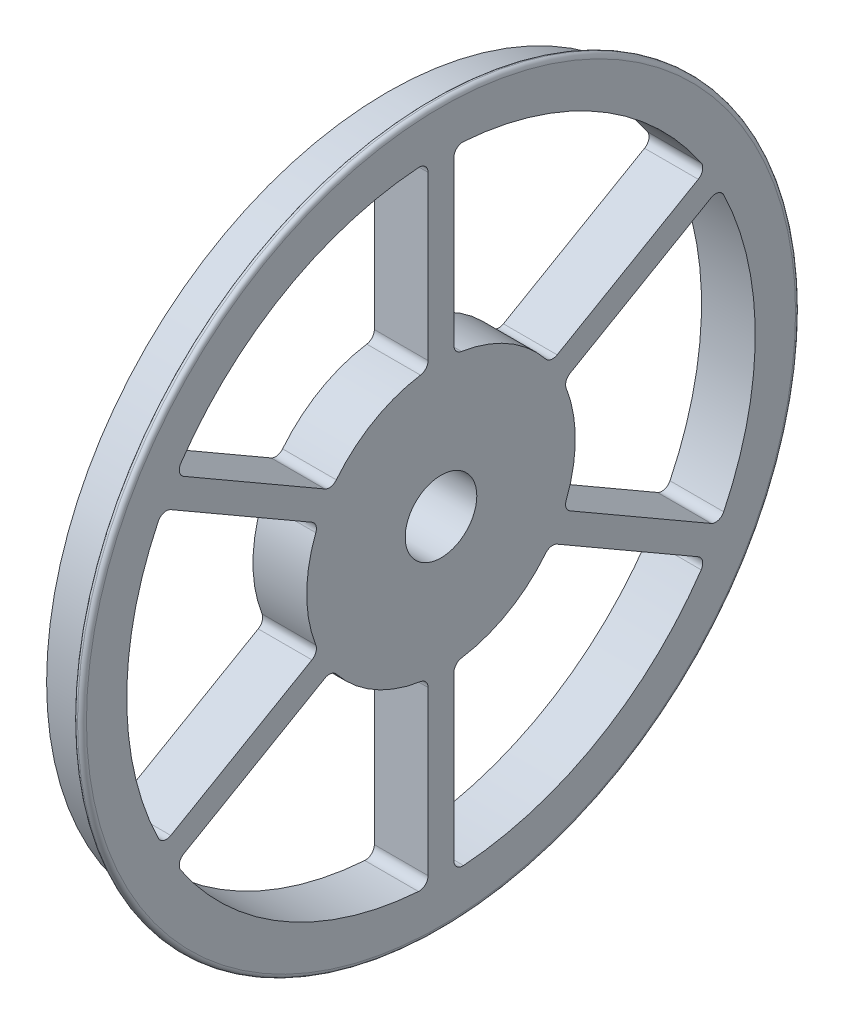
SolidWorks part; units mm, degrees
ref_plane "Front Plane" through (0, 0, 0) normal (0, 0, 1) x (1, 0, 0)
ref_plane "Top Plane" through (0, 0, 0) normal (0, 1, 0) x (1, 0, 0)
ref_plane "Right Plane" through (0, 0, 0) normal (1, 0, 0) x (0, 0, -1)
sketch "Sketch1" plane through (0, 0, 0) normal (0, 0, 1) x (1, 0, 0)
  line L2 (-3, 0) -> (-3, 38.05)
  line L5 (-3, 38.05) -> (2, 38.05)
  line L14 (2, 38.05) -> (2, 40.1)
  line L15 (2, 40.1) -> (3, 40.1)
  line L16 (3, 40.1) -> (3, 0)
  line L17 (3, 0) -> (-3, 0)
  point P0 (0, 0)
  dimension "D3" = 40.1
  dimension "D1" = 1
  dimension "D2" = 5
  dimension "D4" = 38.05
revolve "Revolve2" add sketch "Sketch1" angle 360 about L17
sketch "Sketch2" plane through (3, 0, 0) normal (-1, 0, 0) x (0, 0, 1)
  line L0 (0, 0) -> (13.6518, 0) construction
  line L1 (14.4156, 6.6562) -> (30.1772, 15.7562)
  line L2 (13.6518, 6.2152) -> (13.6518, -6.2152) construction
  line L3 (14.4156, -6.6562) -> (30.1772, -15.7562)
  line L4 (31.0935, 16.2852) -> (31.0935, -16.2852) construction
  line L5 (2.8868, 0) -> (13.6518, 6.2152) construction
  line L6 (2.8868, 0) -> (1.4434, 2.5) construction
  line L7 (1.4434, 2.5) -> (-1.4434, 2.5) construction
  line L8 (-1.4434, 2.5) -> (-2.8868, 0) construction
  line L9 (-2.8868, 0) -> (-1.4434, -2.5) construction
  line L10 (-1.4434, -2.5) -> (1.4434, -2.5) construction
  line L11 (1.4434, -2.5) -> (2.8868, 0) construction
  line L12 (13.6518, 0) -> (31.0935, 0) construction
  line L13 (13.6518, -6.2152) -> (2.8868, 0) construction
  line L14 (12.9722, -9.1562) -> (28.7339, -18.2562)
  line L15 (1.4434, -15.8123) -> (1.4434, -34.0123)
  line L16 (-1.4434, -15.8123) -> (-1.4434, -34.0123)
  line L17 (-12.9722, -9.1562) -> (-28.7339, -18.2562)
  line L18 (-14.4156, -6.6562) -> (-30.1772, -15.7562)
  line L19 (-14.4156, 6.6562) -> (-30.1772, 15.7562)
  line L20 (-12.9722, 9.1562) -> (-28.7339, 18.2562)
  line L21 (-1.4434, 15.8123) -> (-1.4434, 34.0123)
  line L22 (1.4434, 15.8123) -> (1.4434, 34.0123)
  line L23 (12.9722, 9.1562) -> (28.7339, 18.2562)
  arc A0 (31.5769, 15.3268) -> (31.5769, -15.3268) centre (0, 0) cw
  circle A2 centre (0, 0) radius 2.5 construction
  arc A3 (13.9833, 5.4283) -> (13.9833, -5.4283) centre (0, 0) cw
  arc A4 (13.9833, -5.4283) -> (14.4156, -6.6562) centre (14.9156, -5.7901) ccw
  arc A5 (14.4156, 6.6562) -> (13.9833, 5.4283) centre (14.9156, 5.7901) ccw
  arc A6 (30.1772, -15.7562) -> (31.5769, -15.3268) centre (30.6772, -14.8901) ccw
  arc A7 (31.5769, 15.3268) -> (30.1772, 15.7562) centre (30.6772, 14.8901) ccw
  arc A8 (29.0618, -19.683) -> (28.7339, -18.2562) centre (28.2339, -19.1222) ccw
  arc A9 (29.0618, -19.683) -> (2.515, -35.0098) centre (0, 0) cw
  arc A10 (1.4434, -34.0123) -> (2.515, -35.0098) centre (2.4434, -34.0123) ccw
  arc A11 (2.2907, -14.8241) -> (1.4434, -15.8123) centre (2.4434, -15.8123) ccw
  arc A12 (11.6927, -9.3958) -> (2.2907, -14.8241) centre (0, 0) cw
  arc A13 (12.9722, -9.1562) -> (11.6927, -9.3958) centre (12.4722, -10.0222) ccw
  arc A14 (-2.515, -35.0098) -> (-1.4434, -34.0123) centre (-2.4434, -34.0123) ccw
  arc A15 (-2.515, -35.0098) -> (-29.0618, -19.683) centre (0, 0) cw
  arc A16 (-28.7339, -18.2562) -> (-29.0618, -19.683) centre (-28.2339, -19.1222) ccw
  arc A17 (-11.6927, -9.3958) -> (-12.9722, -9.1562) centre (-12.4722, -10.0222) ccw
  arc A18 (-2.2907, -14.8241) -> (-11.6927, -9.3958) centre (0, 0) cw
  arc A19 (-1.4434, -15.8123) -> (-2.2907, -14.8241) centre (-2.4434, -15.8123) ccw
  arc A20 (-31.5769, -15.3268) -> (-30.1772, -15.7562) centre (-30.6772, -14.8901) ccw
  arc A21 (-31.5769, -15.3268) -> (-31.5769, 15.3268) centre (0, 0) cw
  arc A22 (-30.1772, 15.7562) -> (-31.5769, 15.3268) centre (-30.6772, 14.8901) ccw
  arc A23 (-13.9833, 5.4283) -> (-14.4156, 6.6562) centre (-14.9156, 5.7901) ccw
  arc A24 (-13.9833, -5.4283) -> (-13.9833, 5.4283) centre (0, 0) cw
  arc A25 (-14.4156, -6.6562) -> (-13.9833, -5.4283) centre (-14.9156, -5.7901) ccw
  arc A26 (-29.0618, 19.683) -> (-28.7339, 18.2562) centre (-28.2339, 19.1222) ccw
  arc A27 (-29.0618, 19.683) -> (-2.515, 35.0098) centre (0, 0) cw
  arc A28 (-1.4434, 34.0123) -> (-2.515, 35.0098) centre (-2.4434, 34.0123) ccw
  arc A29 (-2.2907, 14.8241) -> (-1.4434, 15.8123) centre (-2.4434, 15.8123) ccw
  arc A30 (-11.6927, 9.3958) -> (-2.2907, 14.8241) centre (0, 0) cw
  arc A31 (-12.9722, 9.1562) -> (-11.6927, 9.3958) centre (-12.4722, 10.0222) ccw
  arc A32 (2.515, 35.0098) -> (1.4434, 34.0123) centre (2.4434, 34.0123) ccw
  arc A33 (2.515, 35.0098) -> (29.0618, 19.683) centre (0, 0) cw
  arc A34 (28.7339, 18.2562) -> (29.0618, 19.683) centre (28.2339, 19.1222) ccw
  arc A35 (11.6927, 9.3958) -> (12.9722, 9.1562) centre (12.4722, 10.0222) ccw
  arc A36 (2.2907, 14.8241) -> (11.6927, 9.3958) centre (0, 0) cw
  arc A37 (1.4434, 15.8123) -> (2.2907, 14.8241) centre (2.4434, 15.8123) ccw
  circle A39 centre (0, 0) radius 40.1 construction
  point P92 (0, 0)
  dimension "D5" = 5
  dimension "D2" = 15
  dimension "D3" = 1
  dimension "D1" = 30
  dimension "D4" = 5
  dimension "D6" = 6
extrude "Cut-Extrude2" cut sketch "Sketch2" along normal through all
fillet "Fillet1" radius 0.5 3 edges at (3, 0, -40.1) (2, 0, -40.1) (2, 0, -38.05)
sketch "Sketch7" plane through (3, 0, 0) normal (1, 0, 0) x (0, 0, -1)
  circle A0 centre (0, 0) radius 4
  dimension "D1" = 8
extrude "Cut-Extrude5" cut sketch "Sketch7" against normal through all both and the other way through all
sketch "Sketch8" plane through (-3, 0, 0) normal (1, 0, 0) x (0, 0, -1)
  circle A0 centre (0, 0) radius 11.25
  dimension "D1" = 22.5
equation "\"SpokeWidth\"= 5"
equation "\"D5@Sketch2\" = \"SpokeWidth\""
equation "\"HubDiameter\"= 30"
equation "\"D2@Sketch2\"=\"HubDiameter\"/2"
equation "\"PulleyDiameter\"= 3in"
equation "\"PulleyWidth\"= 3.45in"
equation "\"RimWidth\"= 5"
equation "\"D4@Sketch2\"=\"RimWidth\""
